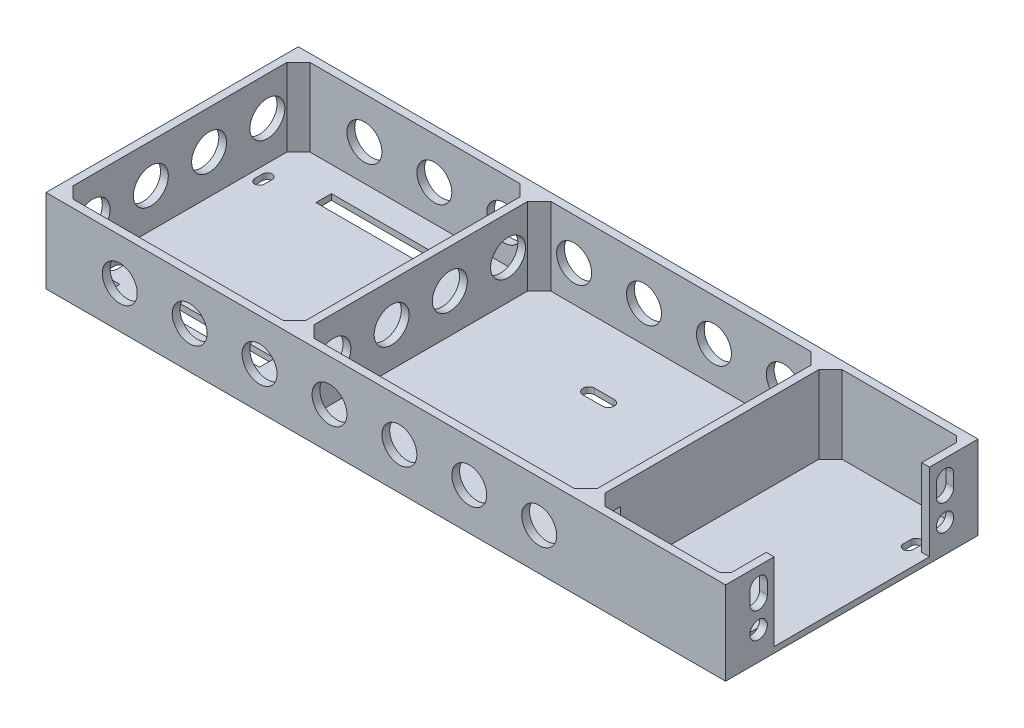
SolidWorks part; units mm, degrees
ref_plane "Спереди" through (0, 0, 0) normal (0, 0, 1) x (1, 0, 0)
ref_plane "Сверху" through (0, 0, 0) normal (0, 1, 0) x (1, 0, 0)
ref_plane "Справа" through (0, 0, 0) normal (1, 0, 0) x (0, 0, -1)
sketch "Эскиз1" plane through (0, 0, 0) normal (0, 1, 0) x (1, 0, 0)
  line L1 (-87.5, -32.5) -> (87.5, -32.5)
  line L2 (-87.5, -32.5) -> (-87.5, 32.5)
  line L3 (-87.5, 32.5) -> (87.5, 32.5)
  line L4 (87.5, -32.5) -> (87.5, 32.5)
  line L5 (-87.5, -32.5) -> (87.5, 32.5) construction
  line L6 (-87.5, 32.5) -> (87.5, -32.5) construction
  point P0 (0, 0)
  dimension "D1" = 175
  dimension "D2" = 65
extrude "Бобышка-Вытянуть1" add sketch "Эскиз1" along normal blind 1.5
sketch "Эскиз3" plane through (0, 1.5, 0) normal (0, 1, 0) x (1, 0, 0)
  line L5 (-87.5, -32.5) -> (87.5, -32.5)
  line L6 (-87.5, -32.5) -> (-87.5, 32.5)
  line L7 (-87.5, 32.5) -> (87.5, 32.5)
  line L8 (85.5, -30.5) -> (85.5, 30.5)
  line L9 (85.5, 30.5) -> (-85.5, 30.5)
  line L10 (-85.5, 30.5) -> (-85.5, -30.5)
  line L11 (-85.5, -30.5) -> (85.5, -30.5)
  line L12 (85.5, -30.5) -> (85.5, 30.5)
  line L13 (85.5, 30.5) -> (-85.5, 30.5)
  line L14 (-85.5, 30.5) -> (-85.5, -30.5)
  line L15 (-85.5, -30.5) -> (85.5, -30.5)
  line L16 (87.5, -32.5) -> (87.5, 32.5)
  line L17 (-87.5, -32.5) -> (87.5, 32.5) construction
  line L18 (-87.5, 32.5) -> (87.5, -32.5) construction
  point P0 (0, 0)
  dimension "D1" = 2
extrude "Бобышка-Вытянуть2" add sketch "Эскиз3" along normal blind 20
sketch "Эскиз4" plane through (87.5, 0, 0) normal (1, 0, 0) x (0, 0, -1)
  line L7 (-32.5, 21.5) -> (32.5, 21.5) construction
  line L8 (-20, 21.5) -> (20, 21.5)
  line L9 (-20, 21.5) -> (-20, 1.5)
  line L10 (-20, 1.5) -> (20, 1.5)
  line L11 (20, 21.5) -> (20, 1.5)
  line L12 (-32.5, 21.5) -> (-32.5, 0) construction
  dimension "D1" = 40
  dimension "D2" = 20
  dimension "D3" = 12.5
extrude "Вырез-Вытянуть1" cut sketch "Эскиз4" against normal blind 2
sketch "Эскиз5" plane through (0, 1.5, 0) normal (0, 1, 0) x (1, 0, 0)
  line L0 (57.5, 20) -> (57.5, 30.5)
  line L1 (87.5, 20) -> (57.5, 20)
  line L2 (87.5, 20) -> (87.5, -20)
  line L3 (87.5, -20) -> (57.5, -20)
  line L4 (57.5, 20) -> (57.5, -20)
  line L5 (85.5, 30.5) -> (-85.5, 30.5) construction
  line L6 (57.5, -20) -> (57.5, -30.5)
  line L7 (-85.5, -30.5) -> (85.5, -30.5) construction
  dimension "D1" = 30
  dimension "D2" = 40
sketch "Эскиз6" plane through (87.5, 0, 0) normal (1, 0, 0) x (0, 0, -1)
  line L0 (-32.5, 21.5) -> (-20, 21.5) construction
  line L1 (-20, 21.5) -> (-20, 1.5) construction
  line L2 (-24, 16.9184) -> (-24, 13.9184) construction
  line L3 (-21.75, 16.9184) -> (-21.75, 13.9184)
  line L4 (-26.25, 16.9184) -> (-26.25, 13.9184)
  circle A1 centre (-24, 7.25) radius 2.25
  arc A2 (-21.75, 16.9184) -> (-26.25, 16.9184) centre (-24, 16.9184) ccw
  arc A3 (-26.25, 13.9184) -> (-21.75, 13.9184) centre (-24, 13.9184) ccw
  point P8 (-24, 15.4184)
  dimension "D1" = 4.5
  dimension "D3" = 4.5
  dimension "D2" = 3
  dimension "D4" = 14.25
  dimension "D6" = 4
extrude "Вырез-Вытянуть2" cut sketch "Эскиз6" against normal blind 2
ref_plane "Плоскость2" through (0, 0, 0) normal (0, 0, -1) x (-1, 0, 0)
mirror "Зеркальное отражение2" about plane through (0, 0, 0) normal (0, 0, -1) of "Вырез-Вытянуть2"
sketch "Эскиз9" plane through (0, 1.5, 0) normal (0, 1, 0) x (1, 0, 0)
  line L0 (85.5, 20) -> (85.5, 30.5) construction
  line L1 (49.5, 30.5) -> (51.5, 30.5)
  line L2 (49.5, 30.5) -> (49.5, -30.5)
  line L3 (49.5, -30.5) -> (51.5, -30.5)
  line L4 (51.5, 30.5) -> (51.5, -30.5)
  line L5 (85.5, 30.5) -> (-85.5, 30.5) construction
  line L6 (-85.5, -30.5) -> (85.5, -30.5) construction
  dimension "D1" = 2
  dimension "D2" = 34
  dimension "D3" = 0
  dimension "D4" = 0
extrude "Бобышка-Вытянуть4" add sketch "Эскиз9" along normal blind 20
sketch "Эскиз12" plane through (51.5, 0, 0) normal (1, 0, 0) x (0, 0, -1)
  line L0 (-30.5, 21.5) -> (30.5, 21.5) construction
  line L1 (-27.5, 16.5) -> (-23.5, 16.5)
  line L2 (-27.5, 16.5) -> (-27.5, 6.5)
  line L3 (-27.5, 6.5) -> (-23.5, 6.5)
  line L4 (-23.5, 16.5) -> (-23.5, 6.5)
  line L5 (-30.5, 21.5) -> (-30.5, 1.5) construction
  dimension "D1" = 10
  dimension "D2" = 4
  dimension "D3" = 5
  dimension "D4" = 3
extrude "Вырез-Вытянуть4" cut sketch "Эскиз12" against normal blind 2
chamfer "Фаска1" distance 3 angle 45 4 edges at (-85.5, 11.5, -30.5) (49.5, 11.5, 30.5) (49.5, 11.5, -30.5) (-85.5, 11.5, 30.5)
chamfer "Фаска2" distance 3 angle 45 2 edges at (51.5, 11.5, -30.5) (51.5, 11.5, 30.5)
chamfer "Фаска3" distance 1.5 angle 45 2 edges at (85.5, 11.5, 30.5) (85.5, 11.5, -30.5)
sketch "Эскиз13" plane through (0, 0, -32.5) normal (0, 0, -1) x (-1, 0, 0)
  line L21 (-87.5, 10.75) -> (86.3564, 10.75) construction
  line L22 (-87.5, 21.5) -> (-87.5, 0) construction
  line L23 (-49.5, 16.5) -> (-49.5, 21.5) construction
  circle A0 centre (-39.5, 10.75) radius 4.5
  dimension "D2" = 9
  dimension "D1" = 10
extrude "Вырез-Вытянуть5" cut sketch "Эскиз13" against normal blind 71
ref_plane "Плоскость3" through (39.5, 0, 0) normal (-1, 0, 0) x (0, 0, 1)
pattern_linear "Линейный массив1" count 7 spacing 18 along (-1, 0, 0) of "Вырез-Вытянуть5"
sketch "Эскиз14" plane through (0, 1.5, 0) normal (0, 1, 0) x (1, 0, 0)
  line L0 (-85.5, 27.5) -> (-85.5, -27.5) construction
  line L1 (-25.5, 30.5) -> (-23.5, 30.5)
  line L2 (-25.5, 30.5) -> (-25.5, -30.5)
  line L3 (-25.5, -30.5) -> (-23.5, -30.5)
  line L4 (-23.5, 30.5) -> (-23.5, -30.5)
  line L5 (46.5, 30.5) -> (-82.5, 30.5) construction
  line L6 (-82.5, -30.5) -> (46.5, -30.5) construction
  point P6 (-24.5, 30.5)
  dimension "D1" = 60
  dimension "D2" = 0
  dimension "D3" = 0
  dimension "D4" = 2
extrude "Бобышка-Вытянуть5" add sketch "Эскиз14" along normal blind 20
chamfer "Фаска4" distance 3 angle 45 2 edges at (-25.5, 11.5, 30.5) (-25.5, 11.5, -30.5)
chamfer "Фаска5" distance 3 angle 45 2 edges at (-23.5, 11.5, 30.5) (-23.5, 11.5, -30.5)
sketch "Эскиз15" plane through (-23.5, 0, 0) normal (1, 0, 0) x (0, 0, -1)
  line L20 (-27.5, 11.5) -> (27.5, 11.5) construction
  line L33 (-27.5, 21.5) -> (-27.5, 1.5) construction
  line L34 (27.5, 1.5) -> (27.5, 21.5) construction
  circle A0 centre (-22.5, 11.5) radius 4.5
  dimension "D1" = 9
  dimension "D2" = 5
extrude "Вырез-Вытянуть6" cut sketch "Эскиз15" against normal blind 71
pattern_linear "Линейный массив2" count 4 spacing 15 along (0, 0, -1) of "Вырез-Вытянуть6"
sketch "Эскиз16" plane through (0, 1.5, 0) normal (0, 1, 0) x (1, 0, 0)
  line L3 (6.8, 13) -> (11.8, 13) construction
  line L4 (6.8, 14.5) -> (11.8, 14.5)
  line L5 (6.8, 11.5) -> (11.8, 11.5)
  line L7 (46.5, 30.5) -> (-20.5, 30.5) construction
  line L8 (39.5, 13) -> (44.5, 13) construction
  line L9 (39.5, 14.5) -> (44.5, 14.5)
  line L10 (39.5, 11.5) -> (44.5, 11.5)
  line L11 (49.5, 27.5) -> (49.5, -27.5) construction
  arc A2 (6.8, 14.5) -> (6.8, 11.5) centre (6.8, 13) ccw
  arc A3 (11.8, 11.5) -> (11.8, 14.5) centre (11.8, 13) ccw
  arc A4 (39.5, 14.5) -> (39.5, 11.5) centre (39.5, 13) ccw
  arc A5 (44.5, 11.5) -> (44.5, 14.5) centre (44.5, 13) ccw
  point P2 (9.3, 13)
  point P11 (42, 13)
  dimension "D1" = 5
  dimension "D2" = 3
  dimension "D3" = 16
  dimension "D4" = 16
  dimension "D5" = 5
  dimension "D6" = 5
  dimension "D7" = 32.7
extrude "Вырез-Вытянуть7" cut sketch "Эскиз16" against normal blind 4
sketch "Эскиз17" plane through (0, 1.5, 0) normal (0, 1, 0) x (1, 0, 0)
  line L1 (-21.4057, 21.2837) -> (3.5943, 21.2837)
  line L2 (-21.4057, 21.2837) -> (-21.4057, -18.7163)
  line L3 (-21.4057, -18.7163) -> (3.5943, -18.7163)
  line L4 (3.5943, 21.2837) -> (3.5943, -18.7163)
  dimension "D1" = 25
  dimension "D2" = 40
sketch "Эскиз18" plane through (0, 1.5, 0) normal (0, 1, 0) x (1, 0, 0)
  line L1 (-70.5, 24) -> (-43.5, 24)
  line L2 (-70.5, 24) -> (-70.5, 20)
  line L3 (-70.5, 20) -> (-43.5, 20)
  line L4 (-43.5, 24) -> (-43.5, 20)
  line L5 (-68.0533, -20) -> (-41.0533, -20)
  line L6 (-68.0533, -20) -> (-68.0533, -24)
  line L7 (-68.0533, -24) -> (-41.0533, -24)
  line L8 (-41.0533, -20) -> (-41.0533, -24)
  line L9 (-28.5, 30.5) -> (-82.5, 30.5) construction
  line L12 (-85.5, 27.5) -> (-85.5, -27.5) construction
  dimension "D1" = 40
  dimension "D2" = 6.5
  dimension "D3" = 4
  dimension "D4" = 4
  dimension "D5" = 15
  dimension "D6" = 27
extrude "Вырез-Вытянуть8" cut sketch "Эскиз18" against normal blind 5
sketch "Эскиз19" plane through (0, 1.5, 0) normal (0, 1, 0) x (1, 0, 0)
  line L0 (82.5, 21.5) -> (82.5, 19.5) construction
  line L1 (83.75, 21.5) -> (83.75, 19.5)
  line L2 (81.25, 21.5) -> (81.25, 19.5)
  line L3 (82.5, -18.5) -> (82.5, -20.5) construction
  line L4 (83.75, -18.5) -> (83.75, -20.5)
  line L5 (81.25, -18.5) -> (81.25, -20.5)
  line L6 (82.5, 30.5) -> (82.5, -30.5) construction
  line L7 (84, 30.5) -> (54.5, 30.5) construction
  line L8 (54.5, -30.5) -> (84, -30.5) construction
  line L9 (85.5, 20) -> (85.5, 29) construction
  line L10 (-82.5, 30.5) -> (-82.5, -30.5) construction
  line L11 (-28.5, 30.5) -> (-82.5, 30.5) construction
  line L12 (-82.5, -30.5) -> (-28.5, -30.5) construction
  line L13 (-85.5, 27.5) -> (-85.5, -27.5) construction
  line L15 (-82.5, 19.5) -> (-82.5, 17.5) construction
  line L16 (-81.25, 19.5) -> (-81.25, 17.5)
  line L17 (-83.75, 19.5) -> (-83.75, 17.5)
  line L18 (-82.5, -18.5) -> (-82.5, -20.5) construction
  line L19 (-81.25, -18.5) -> (-81.25, -20.5)
  line L20 (-83.75, -18.5) -> (-83.75, -20.5)
  arc A0 (83.75, 21.5) -> (81.25, 21.5) centre (82.5, 21.5) ccw
  arc A1 (81.25, 19.5) -> (83.75, 19.5) centre (82.5, 19.5) ccw
  arc A2 (83.75, -18.5) -> (81.25, -18.5) centre (82.5, -18.5) ccw
  arc A3 (81.25, -20.5) -> (83.75, -20.5) centre (82.5, -20.5) ccw
  arc A4 (-81.25, 19.5) -> (-83.75, 19.5) centre (-82.5, 19.5) ccw
  arc A5 (-83.75, 17.5) -> (-81.25, 17.5) centre (-82.5, 17.5) ccw
  arc A6 (-81.25, -18.5) -> (-83.75, -18.5) centre (-82.5, -18.5) ccw
  arc A7 (-83.75, -20.5) -> (-81.25, -20.5) centre (-82.5, -20.5) ccw
  point P2 (82.5, 20.5)
  point P9 (82.5, -19.5)
  point P22 (89.1382, 17.8711)
  point P23 (-75.807, 19.5)
  point P24 (0, 0)
  point P35 (-82.5, 18.5)
  point P42 (-82.5, -19.5)
  point P49 (-80.7592, 10.3542)
  dimension "D1" = 2
  dimension "D2" = 2.5
  dimension "D3" = 40
  dimension "D4" = 10
  dimension "D5" = 3
  dimension "D6" = 3
  dimension "D7" = 2.5
  dimension "D8" = 2
  dimension "D9" = 2
  dimension "D10" = 2.5
  dimension "D11" = 40
  dimension "D12" = 10
extrude "Вырез-Вытянуть9" cut sketch "Эскиз19" against normal blind 10
sketch "Эскиз21" plane through (0, 1.5, 0) normal (0, 1, 0) x (1, 0, 0)
  line L0 (85.5, -29) -> (85.5, -20) construction
  line L1 (82.5, -23.5) -> (76.5, -23.5)
  line L2 (82.5, -23.5) -> (82.5, -29.5)
  line L3 (82.5, -29.5) -> (76.5, -29.5)
  line L4 (76.5, -23.5) -> (76.5, -29.5)
  line L5 (54.5, -30.5) -> (84, -30.5) construction
  dimension "D1" = 6
  dimension "D2" = 6
  dimension "D3" = 3
  dimension "D4" = 1
extrude "Вырез-Вытянуть10" cut sketch "Эскиз21" against normal blind 10
pattern_linear "Линейный массив3" count 2 spacing 160 along (-1, 0, 0) of "Вырез-Вытянуть10"
